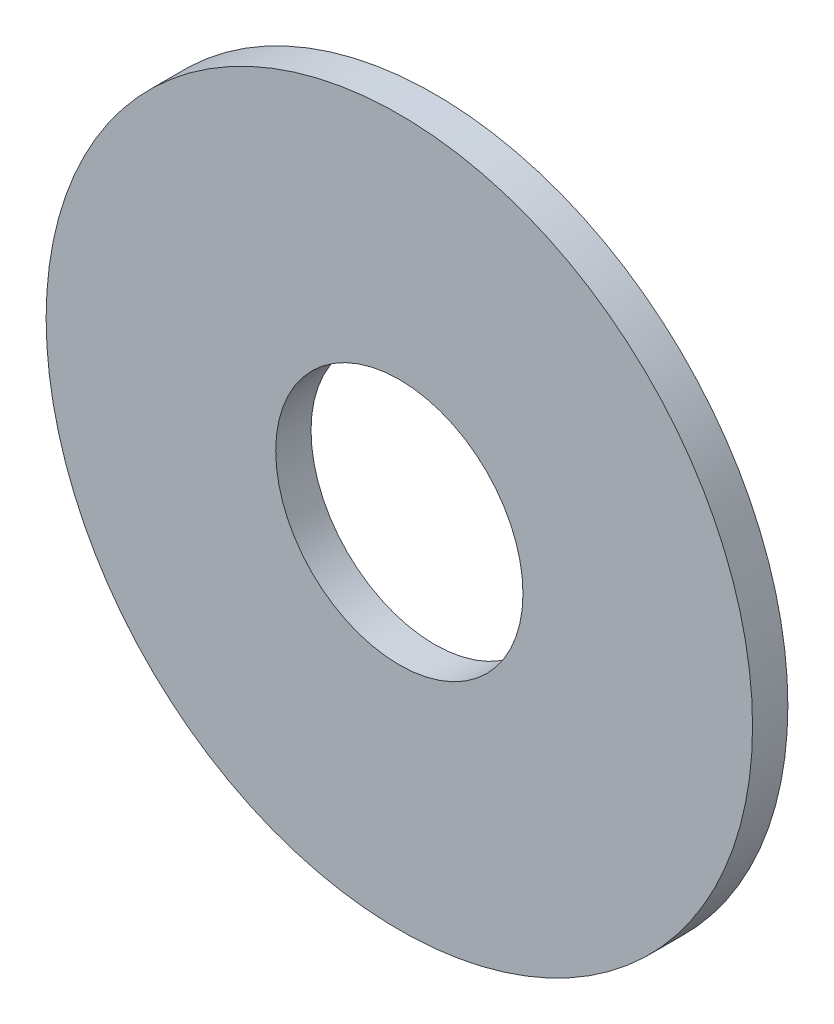
SolidWorks part; units mm, degrees
material "Сталь ШХ15 ГОСТ 801-78"
ref_plane "Plane1" through (0, 0, 0) normal (0, 0, 1) x (1, 0, 0)
ref_plane "Plane2" through (0, 0, 0) normal (0, 1, 0) x (1, 0, 0)
ref_plane "Plane3" through (0, 0, 0) normal (1, 0, 0) x (0, 0, -1)
sketch "Эскиз1" plane through (0, 0, 0) normal (0, 0, 1) x (1, 0, 0)
  circle A0 centre (0, 0) radius 10
  circle A1 centre (0, 0) radius 3.5
  dimension "D1" = 20
  dimension "D2" = 7
extrude "Бобышка-Вытянуть1" add sketch "Эскиз1" along normal blind 1 contours A1 | A0 region at (0, 0, 0)
